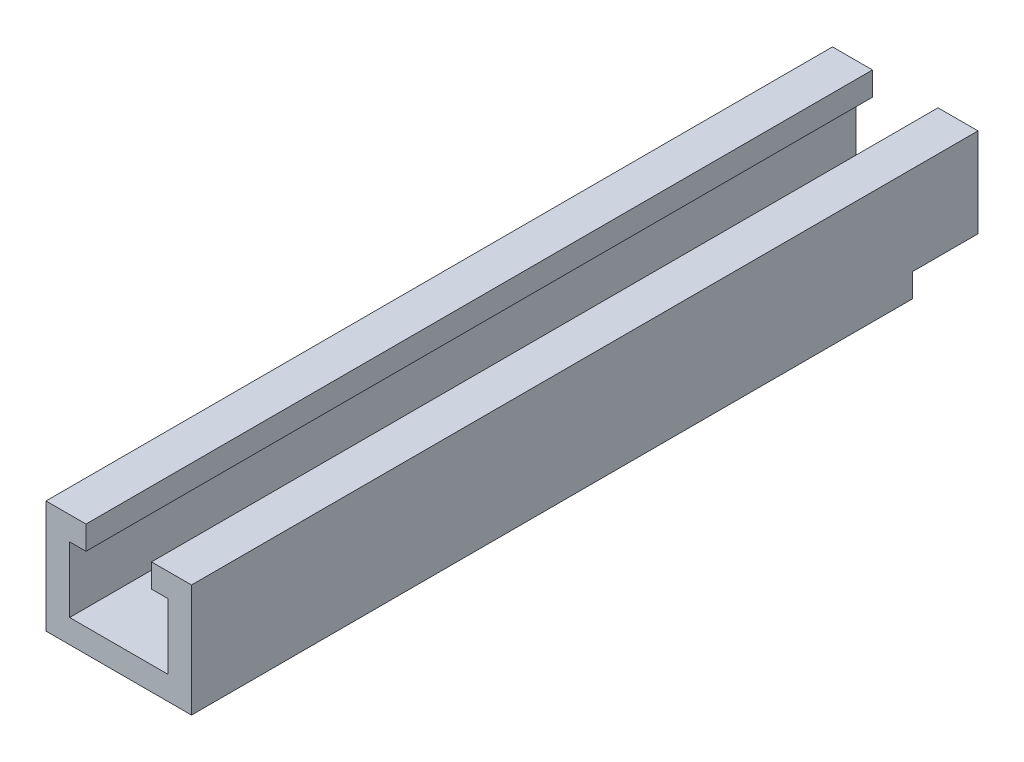
SolidWorks part; units mm, degrees
material "Beech"
ref_plane "Front Plane" through (0, 0, 0) normal (0, 0, 1) x (1, 0, 0)
ref_plane "Top Plane" through (0, 0, 0) normal (0, 1, 0) x (1, 0, 0)
ref_plane "Right Plane" through (0, 0, 0) normal (1, 0, 0) x (0, 0, -1)
sketch "Sketch1" plane through (0, 0, 0) normal (0, 0, 1) x (1, 0, 0)
  line L1 (0, 0) -> (111, 0)
  line L2 (0, 0) -> (0, 18)
  line L3 (0, 18) -> (111, 18)
  line L4 (111, 0) -> (111, 18)
  dimension "D1" = 18
  dimension "D2" = 111
extrude "baseplate" add sketch "Sketch1" along normal blind 600
sketch "Sketch2" plane through (0, 18, 0) normal (0, 1, 0) x (1, 0, 0)
  line L0 (111, -600) -> (0, -600) construction
  line L1 (0, 0) -> (18, 0)
  line L2 (0, 0) -> (0, -600)
  line L3 (0, -600) -> (18, -600)
  line L4 (18, 0) -> (18, -600)
  dimension "D1" = 18
extrude "side_rail" add sketch "Sketch2" along normal blind 50
sketch "Sketch3" plane through (0, 68, 0) normal (0, 1, 0) x (1, 0, 0)
  line L0 (111, -600) -> (18, -600) construction
  line L1 (0, 0) -> (30.5, 0)
  line L2 (0, 0) -> (0, -600)
  line L3 (0, -600) -> (30.5, -600)
  line L4 (30.5, 0) -> (30.5, -600)
  dimension "D1" = 30.5
extrude "keeper rail" add sketch "Sketch3" along normal blind 18
ref_plane "longitudinal midplane" through (55.5, 0, 0) normal (-1, 0, 0) x (0, 0, 1)
mirror "mirror rails" about plane through (55.5, 0, 0) normal (-1, 0, 0) of "keeper rail", "side_rail"
sketch "Sketch5" plane through (0, 0, 0) normal (0, -1, 0) x (1, 0, 0)
  line L0 (111, 600) -> (111, 0) construction
  line L1 (0, 0) -> (111, 0)
  line L2 (0, 0) -> (0, 50)
  line L3 (0, 50) -> (111, 50)
  line L4 (111, 0) -> (111, 50)
  dimension "D1" = 50
extrude "lap joint cutout" cut sketch "Sketch5" against normal blind 18
hole_wizard "lap joint bolt hole pattern" positions "Sketch7" profile "Sketch9" tap size "M5x0.8" standard "ANSI Metric"
sketch "Sketch7" plane through (0, 18, 0) normal (0, -1, 0) x (-1, 0, 0)
  line L1 (-102, -10) -> (-9, -10)
  line L2 (-102, -10) -> (-102, -40)
  line L3 (-102, -40) -> (-9, -40)
  line L4 (-9, -10) -> (-9, -40)
  line L5 (-102, 0) -> (-102, -10)
  line L6 (-93, 0) -> (-111, 0) construction
  line L8 (-9, -10) -> (-9, 0)
  line L9 (0, 0) -> (-18, 0) construction
  line L10 (-9, -25) -> (0, -25)
  line L11 (0, -50) -> (0, 0) construction
  point P1 (-102, -10)
  point P2 (-9, -40)
  point P113 (-102, -40)
  point P114 (-9, -10)
sketch "Sketch9" plane through (102, 18, 10) normal (1, 0, 0) x (0, 0, -1)
  line L0 (0, 0) -> (0, 15.2618)
  line L1 (0, 15.2618) -> (2.1, 14)
  line L2 (2.1, 14) -> (2.1, 0)
  line L5 (2.1, 0) -> (0, 0)
  line L10 (0, 15.2618) -> (-2.1, 14) construction
  line L11 (0, -6.35) -> (0, 107.95) construction
  dimension "Tap Drill Dia." = 4.2
  dimension "Tap Drill Depth" = 14
  dimension "Drill Angle" = 118
hole_wizard "M6 Clearance Hole1" positions "Sketch10" profile "Sketch11" hole size "M6" standard "ANSI Metric" end condition through all
sketch "Sketch10" plane through (0, 18, 0) normal (0, 1, 0) x (1, 0, 0)
  line L0 (37.5, -535) -> (73.5, -535)
  line L2 (55.5, -535) -> (55.5, -600)
  line L3 (93, -600) -> (18, -600) construction
  point P0 (37.5, -535)
  point P2 (73.5, -535)
  dimension "D1" = 36
  dimension "D2" = 65
sketch "Sketch11" plane through (37.5, 18, 535) normal (1, 0, 0) x (0, 0, 1)
  line L0 (0, 0) -> (0, 18)
  line L1 (0, 18) -> (3.3, 18)
  line L2 (3.3, 18) -> (3.3, 0)
  line L5 (3.3, 0) -> (0, 0)
  line L11 (0, -6.35) -> (0, 107.95) construction
  dimension "Thru Hole Dia." = 6.6
  dimension "Thru Hole Depth" = 18
equation "\"board_thickness\" = 18mm"
equation "\"way_width\"= 75mm"
equation "\"way_thickness\"= 50mm"
equation "\"radial_clearance\"= 0.1mm"
equation "\"slider_width\"= \"way_width\"-2* \"radial_clearance\""
equation "\"slider_thickness\" = \"way_thickness\" - 2 * \"radial_clearance\""
equation "\"column_width\"= \"way_width\" + 2 * \"board_thickness\""
equation "\"D1@Sketch1\"=\"board_thickness\""
equation "\"D2@Sketch1\"=\"column_width\""
equation "\"D1@Sketch2\"=\"board_thickness\""
equation "\"D1@keeper rail\"=\"board_thickness\""
equation "\"boxway_slot_width\" = 50mm"
equation "\"keeper_rail_width\" = (\"column_width\" - \"boxway_slot_width\")/2"
equation "\"D1@Sketch3\"=\"keeper_rail_width\""
equation "\"slider_length\" = 125mm"
equation "\"nut_diameter\"= 22mm"
equation "\"nut_length\"= 15mm"
equation "\"leadscrew_diameter\"= 10mm"
equation "\"leadscrew_radial_clearance\"= 1mm"
equation "\"bearing_bolt_pattern_width\" = 30mm"
equation "\"bearing_bolt_pattern_height\" = 75mm"
equation "\"desktop_bolt_pattern_width\" = 30mm"
equation "\"desktop_bolt_pattern_height\" = 30mm"
equation "\"bearing_bolt_nut_counterbore_diameter\" = 12mm"
equation "\"bearing_bolt_nut_counterbore_depth\"= 10mm"
equation "\"desktop_depth\"= 500mm"
equation "\"desktop_width\"= 650mm"
equation "\"desktop_thickness\"= 18mm"
equation "\"leg_height\"=100mm"
equation "\"leg_width\"=18mm"
equation "\"leg_length\"=500mm"
equation "\"D1@lap joint cutout\" = \"leg_width\""
equation "\"lap_joint_height\" = 50mm"
equation "\"lap_dowel_diameter\"= 8mm"
equation "\"lap_dowel_hole_z_spacing\"=30"
equation "\"D1@Sketch5\"=\"lap_joint_height\""
equation "\"D1@Sketch7\"=\"lap_dowel_hole_z_spacing\""
